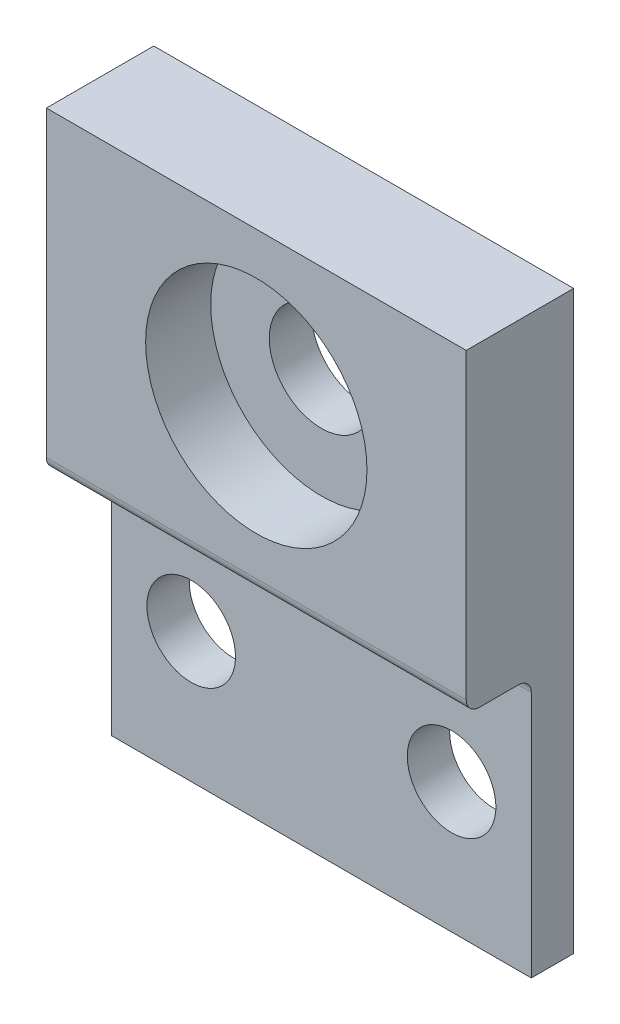
SolidWorks part; units mm, degrees
material "ABS"
ref_plane "Front Plane" through (0, 0, 0) normal (0, 0, 1) x (1, 0, 0)
ref_plane "Top Plane" through (0, 0, 0) normal (0, 1, 0) x (1, 0, 0)
ref_plane "Right Plane" through (0, 0, 0) normal (1, 0, 0) x (0, 0, -1)
sketch "Sketch1" plane through (0, 0, 0) normal (0, 0, 1) x (1, 0, 0)
  line L0 (16.125, 10) -> (16.125, 0) construction
  line L1 (16.125, 10) -> (16.125, 20) construction
  line L3 (6.125, 10) -> (26.125, 10) construction
  line L5 (0, 0) -> (32.25, 0)
  line L6 (0, 0) -> (0, 20)
  line L7 (0, 20) -> (32.25, 20)
  line L8 (32.25, 0) -> (32.25, 20)
  line L13 (0, 32.5) -> (32.25, 32.5) construction
  line L14 (16.125, 41) -> (16.125, 44.25) construction
  line L15 (0, 20) -> (0, 44.25)
  line L16 (0, 44.25) -> (32.25, 44.25)
  line L17 (32.25, 20) -> (32.25, 44.25)
  circle A0 centre (6.125, 10) radius 3.4004
  circle A1 centre (26.125, 10) radius 3.4004
  circle A4 centre (16.125, 32.5) radius 8.5
  circle A5 centre (16.125, 32.5) radius 4
  dimension "D2" = 20
  dimension "D4" = 17
  dimension "D7" = 8
  dimension "D1" = 10
  dimension "D3" = 32.25
  dimension "D5" = 3.25
  dimension "D6" = 12.5
extrude "Boss-Extrude1" add sketch "Sketch1" along normal blind 3.25 contours L5 L8 L7 L6 A1 A0 | L7 L17 L16 L15 A4 | A4 A5 region at (16.125, 10, 0) region at (0.4035, 32.125, 0) region at (7.8654, 32.5, 0)
extrude "Boss-Extrude2" add sketch "Sketch1<3>" along normal blind 8.25 contours L7 L17 L16 L15 A4 region at (0.4035, 32.125, 0)
sketch "Sketch1<3>" plane through (0, 0, 0) normal (0, 0, 1) x (1, 0, 0) same geometry as "Sketch1"
fillet "Fillet1" radius 1 2 edges at (16.125, 20, 8.25) (16.125, 20, 3.25)
